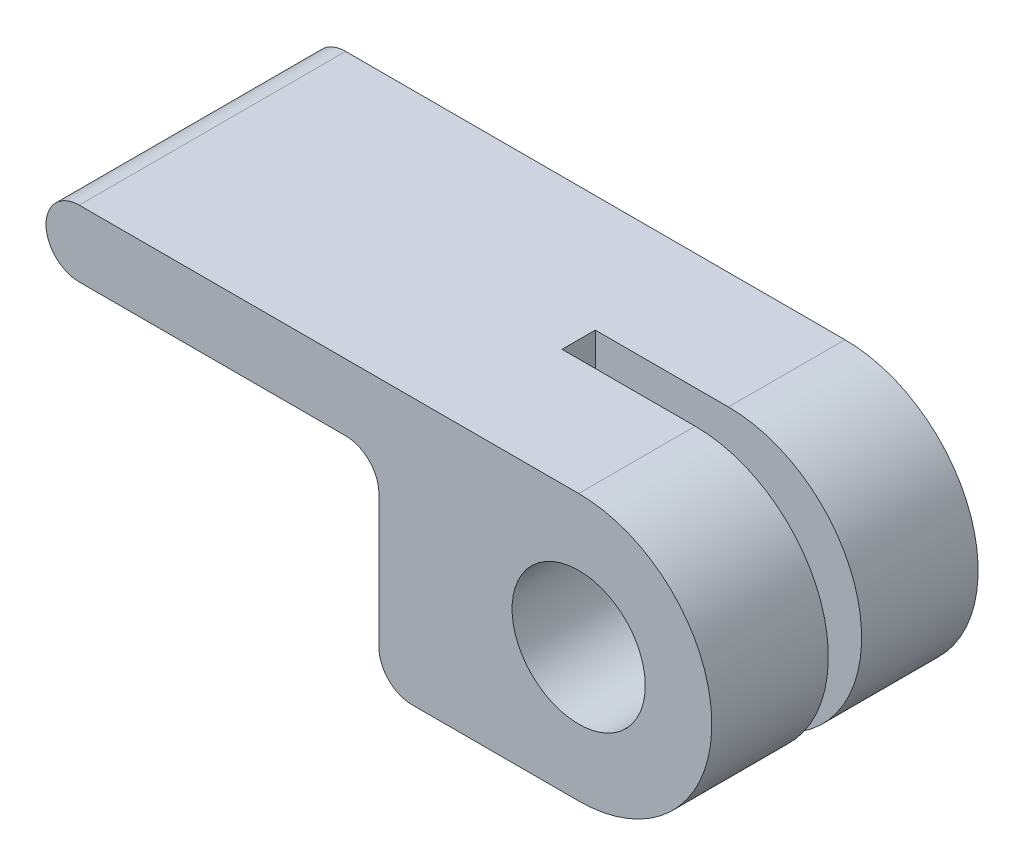
SolidWorks part; units mm, degrees
material "ABS"
ref_plane "Front Plane" through (0, 0, 0) normal (0, 0, 1) x (1, 0, 0)
ref_plane "Top Plane" through (0, 0, 0) normal (0, 1, 0) x (1, 0, 0)
ref_plane "Right Plane" through (0, 0, 0) normal (1, 0, 0) x (0, 0, -1)
sketch "Sketch1" plane through (0, 0, 0) normal (0, 0, 1) x (1, 0, 0)
  line L0 (-6.35, 0) -> (-6.35, 3.175)
  line L1 (0, 3.175) -> (-25.4, 3.175)
  line L2 (-25.4, 3.175) -> (-25.4, 6.35)
  line L3 (-25.4, 6.35) -> (0, 6.35)
  line L4 (-6.35, -6.35) -> (0, -6.35)
  line L5 (-9.525, 3.175) -> (-6.35, 3.175)
  line L6 (-9.525, 3.175) -> (-9.525, -6.35)
  line L7 (-9.525, -6.35) -> (-6.35, -6.35)
  line L8 (-6.35, 3.175) -> (-6.35, -6.35)
  circle A0 centre (0, 0) radius 6.35
  circle A1 centre (0, 0) radius 3.175
  dimension "D1" = 6.35
  dimension "D2" = 12.7
  dimension "D3" = 25.4
extrude "Boss-Extrude1" add sketch "Sketch1" along normal blind 12.7 contours A0 L3 L2 L1 | A1 A0 | A0 L8 L3 | A0 L1 L0 | L8 L0 L1 L6 L7 | A0 L8 L4 region at (-7.9375, -1.5875, 0) region at (-4.9316, -4.9316, 0) region at (-5.9601, 1.597, 0) region at (-6.098, 2.3923, 0) region at (-14.613, 4.8143, 0)
sketch "Sketch2" plane through (0, 0, 12.7) normal (0, 0, 1) x (1, 0, 0)
  line L1 (6.35, -6.35) -> (-6.35, -6.35)
  line L2 (6.35, -6.35) -> (6.35, 6.35)
  line L3 (6.35, 6.35) -> (-6.35, 6.35)
  line L4 (-6.35, -6.35) -> (-6.35, 6.35)
  line L5 (6.35, -6.35) -> (-6.35, 6.35) construction
  line L6 (6.35, 6.35) -> (-6.35, -6.35) construction
  arc A0 (0, -6.35) -> (0, 6.35) centre (0, 0) ccw construction
  point P0 (0, 0)
extrude "Cut-Extrude1" cut sketch "Sketch2" against normal blind 1.5875 from offset 5.5562 offset against normal yes
fillet "Fillet1" radius 1.5875 4 edges at (-9.525, 3.175, 6.35) (-9.525, -6.35, 6.35) (-25.4, 6.35, 6.35) (-25.4, 3.175, 6.35)
